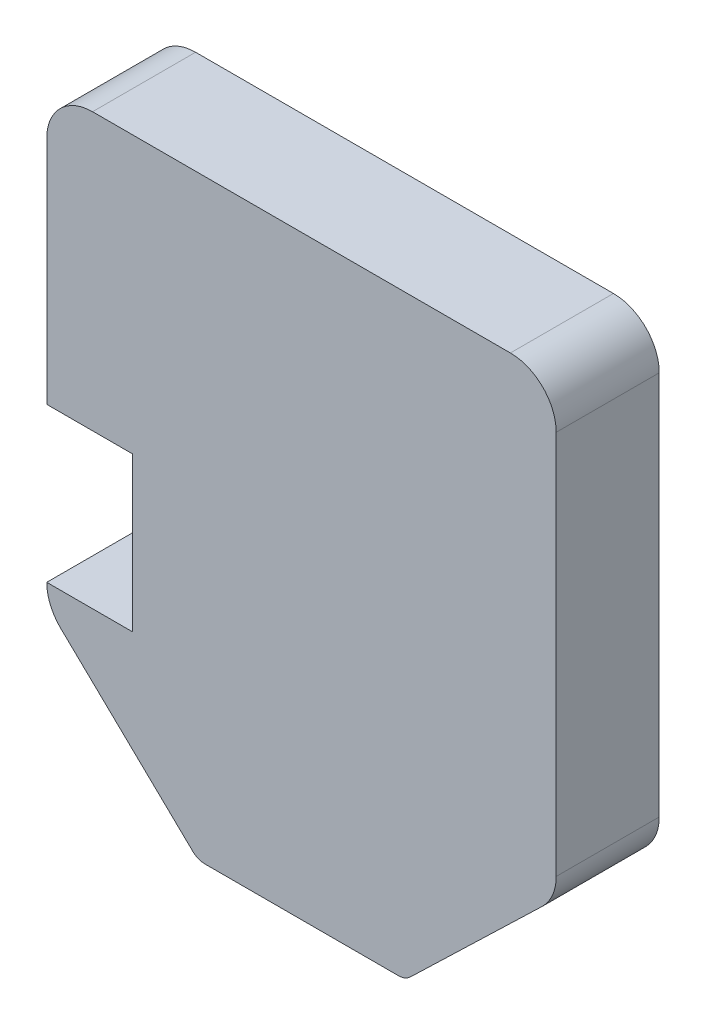
SolidWorks part; units mm, degrees
ref_plane "Front Plane" through (0, 0, 0) normal (0, 0, 1) x (1, 0, 0)
ref_plane "Top Plane" through (0, 0, 0) normal (0, 1, 0) x (1, 0, 0)
ref_plane "Right Plane" through (0, 0, 0) normal (1, 0, 0) x (0, 0, -1)
sketch "Palm_sketch" plane through (0, 0, 0) normal (0, 0, 1) x (1, 0, 0)
  line L0 (0, 78.6026) -> (0.0161, -25.3974)
  line L1 (-36.5, 78.6026) -> (36.5, 78.6026)
  line L2 (-44.5, 70.6026) -> (-44.5, 3.4047)
  line L3 (-16.8916, -25.3974) -> (16.9237, -25.3974)
  line L6 (-42.0464, -2.3605) -> (-18.9715, -24.5594)
  line L7 (42.05, -2.36) -> (19.005, -24.5581)
  line L8 (44.5, 70.6026) -> (44.5, 3.4018)
  line L9 (44.5, 70.6026) -> (44.5, 0)
  line L10 (44.5, 0) -> (19.005, -24.5581)
  arc A0 (-36.5, 78.6026) -> (-44.5, 70.6026) centre (-36.5, 70.6026) ccw
  arc A2 (36.5, 78.6026) -> (44.5, 70.6026) centre (36.5, 70.6026) cw
  arc A3 (-42.0464, -2.3605) -> (-44.5, 3.4047) centre (-36.5, 3.4047) cw
  arc A4 (42.05, -2.36) -> (44.5, 3.4018) centre (36.5, 3.4018) ccw
  arc A5 (-16.8916, -25.3974) -> (-18.9715, -24.5594) centre (-16.8916, -22.3974) cw
  arc A6 (19.005, -24.5581) -> (16.9237, -25.3974) centre (16.9237, -22.3974) cw
  dimension "D3" = 8
  dimension "D4" = 8
  dimension "D2" = 8
  dimension "D5" = 3
  dimension "D6" = 3
  dimension "D1" = 3
  dimension "D9" = 8
  dimension "D7" = 67.1978
  dimension "D8" = 33.8153
extrude "Palm_Body" add sketch "Palm_sketch" along normal mid plane 18 contours L8 A4 L7 A6 L3 A5 L6 A3 L2 A0 L1 A2
ref_axis "MCP_REFERENCE" through (36.5, 78.6026, 0) along (-1, 0, 0)
sketch "Sketch5" plane through (0, 78.6026, 0) normal (0, 1, 0) x (1, 0, 0)
  line L0 (-36.5, 0) -> (36.5, 0)
  line L1 (-36.5, -9) -> (-36.5, 9) construction
  line L2 (36.5, 0) -> (-36.5, 0) construction
  point P7 (-28, 0)
  point P8 (-28, 0)
  point P9 (-8.5, 0)
  point P10 (11, 0)
  point P11 (29, 0)
  dimension "D1" = 8.5
  dimension "D2" = 28
  dimension "D3" = 47.5
  dimension "D4" = 65.5
  dimension "D5" = 73
ref_axis "index" through (-28, 78.6026, 0) along (0, 1, 0)
ref_axis "middle" through (-8.5, 78.6026, 0) along (0, 1, 0)
ref_axis "ring" through (11, 78.6026, 0) along (0, 1, 0)
ref_axis "Little finger" through (29, 78.6026, 0) along (0, 1, 0)
sketch "Sketch6" plane through (-44.5, 0, 0) normal (-1, 0, 0) x (0, 0, 1)
  line L0 (0, 70.6026) -> (0, 3.4047)
  line L1 (9, 70.6026) -> (-9, 70.6026) construction
  line L2 (9, 3.4047) -> (-9, 3.4047) construction
  point P0 (0, 8.6026)
  dimension "D1" = 70
ref_axis "Thumb_CMC_Axis_1" through (-44.5, 8.6026, 0) along (1, 0, 0)
ref_axis "Thumb_CMC_Axis_2" through (-44.5, 8.6026, 0) along (0, 1, 0)
ref_point "wrist point"
ref_axis "Wrist_Axis" through (0.0161, -25.3974, 0) along (1, 0, 0)
ref_point "pinky"
ref_point "ring_point"
ref_point "middle_point"
ref_point "index_point"
ref_axis "index_point+right" through (-28, 78.6026, 0) along (1, 0, 0)
ref_axis "index_point+front" through (-28, 78.6026, 0) along (0, 0, 1)
ref_axis "middle+right" through (-8.5, 78.6026, 0) along (1, 0, 0)
ref_axis "middle_point+front" through (-8.5, 78.6026, 0) along (0, 0, 1)
ref_axis "ring_point+right" through (11, 78.6026, 0) along (1, 0, 0)
ref_axis "ring_point+front" through (11, 78.6026, 0) along (0, 0, 1)
ref_axis "pinky+right" through (29, 78.6026, 0) along (1, 0, 0)
ref_axis "pinky+front" through (29, 78.6026, 0) along (0, 0, 1)
ref_plane "Plane1" through (-44.5, 0, 0) normal (-1, 0, 0) x (0, 0, 1)
sketch "Sketch7" plane through (-44.5, 0, 0) normal (-1, 0, 0) x (0, 0, 1)
  line L0 (-9, 3.4047) -> (9, 3.4047)
  line L1 (9, 3.4047) -> (9, 30.3235)
  line L2 (9, 70.6026) -> (9, 3.4047) construction
  line L3 (9, 30.3235) -> (-9, 30.3235)
  line L4 (-9, 70.6026) -> (-9, 3.4047) construction
  line L5 (-9, 30.3235) -> (-9, 3.4047)
extrude "Boss-Extrude1" add sketch "Sketch7" against normal blind 15 separate body
combine bodies "Combine1" operation type subtract main body 101 bodies to subtract 102
ref_point "thumb"
ref_axis "thumv+right" through (-37, 3.4047, 0) along (1, 0, 0)
ref_axis "thumb+up" through (-37, 3.4047, 0) along (0, 1, 0)
ref_axis "thumb+front" through (-37, 3.4047, 0) along (0, 0, 1)
ref_axis "wrist+top" through (0.0161, -25.3974, 0) along (0, 1, 0)
ref_plane "Plane4" through (0.0161, -25.3974, 0) normal (0, 1, 0) x (1, 0, 0)
ref_plane "Plane5" through (0.0161, -55.3974, 0) normal (0, 1, 0) x (1, 0, 0)
ref_point "ballcenter"
ref_plane "Plane6" through (0.0161, -55.3974, 0) normal (-1, 0, 0) x (0, 0, 1)
ref_axis "flex_axis" through (0.0161, -55.3974, 0) along (-1, 0, 0)
